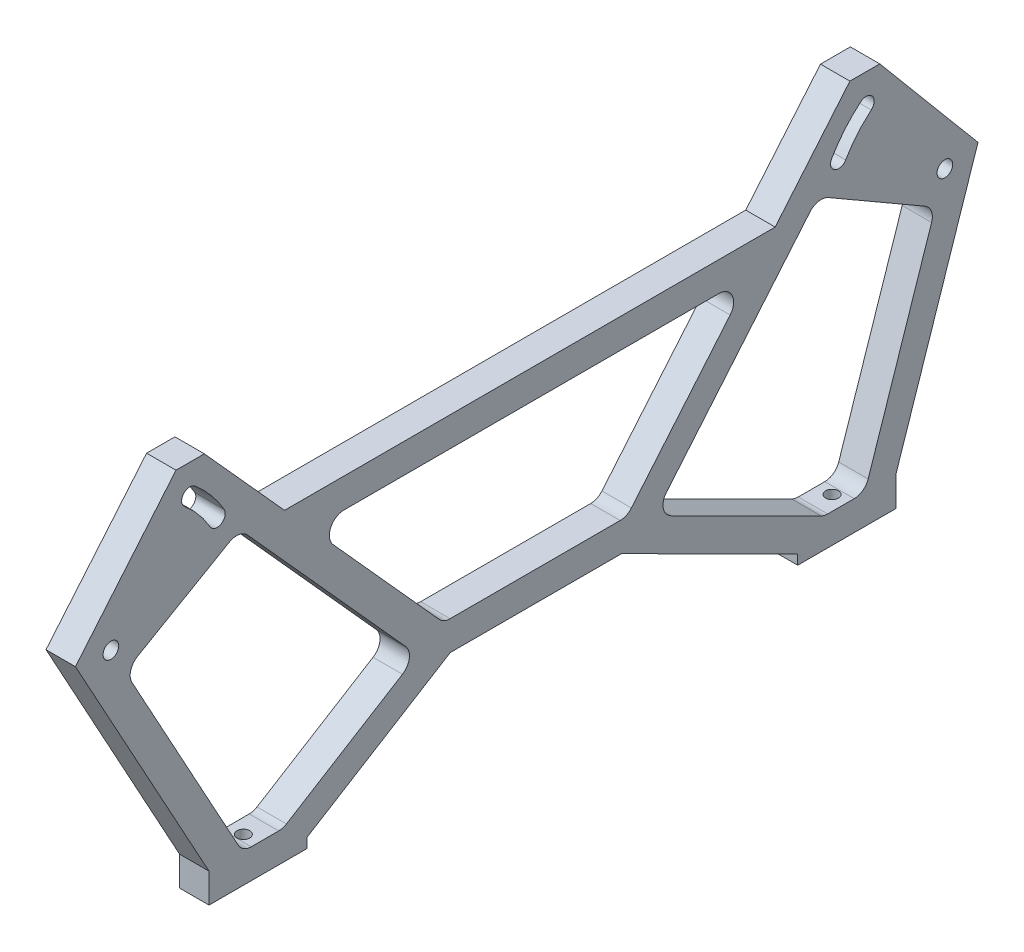
SolidWorks part; units mm, degrees
ref_plane "Front Plane" through (0, 0, 0) normal (0, 0, 1) x (1, 0, 0)
ref_plane "Top Plane" through (0, 0, 0) normal (0, 1, 0) x (1, 0, 0)
ref_plane "Right Plane" through (0, 0, 0) normal (1, 0, 0) x (0, 0, -1)
sketch "Sketch1" plane through (0, 0, 0) normal (1, 0, 0) x (0, 0, -1)
  line L0 (-65, 0) -> (-45, 0)
  line L1 (-45, 0) -> (-45, 2)
  line L2 (-65, 0) -> (-65, 6)
  line L3 (55, 0) -> (75, 0)
  line L4 (75, 0) -> (75, 6)
  line L5 (55, 0) -> (55, 2)
  line L6 (-85, 55) -> (-65.8489, 71.0697) construction
  line L7 (65.8489, 71.0697) -> (85, 55) construction
  line L8 (-68.9303, 74.1511) -> (-85, 55) construction
  line L9 (-85, 55) -> (-63.3494, 67.5) construction
  line L10 (63.3494, 67.5) -> (85, 55) construction
  line L11 (85, 55) -> (68.9303, 74.1511) construction
  line L12 (-65, 6) -> (-92.2327, 55.7147)
  line L13 (-92.2327, 55.7147) -> (-71.7282, 80.1511)
  line L14 (-71.7282, 80.1511) -> (-65.952, 80.1511)
  line L15 (71.7282, 80.1511) -> (91.7528, 56.2866)
  line L16 (91.7528, 56.2866) -> (75, 6)
  line L17 (-58.1588, 6) -> (-49.9434, 6)
  line L18 (-82.1167, 49.7365) -> (-58.7747, 63.213)
  line L19 (-44.2063, 56) -> (45.3715, 56)
  line L20 (59.0991, 63.0257) -> (83.0642, 49.1894)
  line L21 (83.0642, 49.1894) -> (68.6758, 6)
  line L22 (-49.9434, 6) -> (-22.5046, 22.931)
  line L23 (25.8015, 23.343) -> (59.0991, 63.0257)
  line L24 (-15.8286, 20) -> (19.0801, 20)
  line L25 (45.3715, 56) -> (20.1985, 26)
  line L26 (20.1985, 26) -> (-17.1942, 26)
  line L27 (-17.1942, 26) -> (-44.2063, 56)
  line L28 (19.0801, 20) -> (55, 2)
  line L29 (-58.7747, 63.213) -> (-22.5046, 22.931)
  line L30 (-15.8286, 20) -> (-45, 2)
  line L31 (-58.1588, 6) -> (-82.1167, 49.7365)
  line L32 (68.6758, 6) -> (60.4103, 6)
  line L33 (60.4103, 6) -> (25.8015, 23.343)
  line L34 (-15.8286, 20) -> (-26.5479, 31.9049) construction
  line L35 (19.0801, 20) -> (32.4361, 35.917) construction
  line L36 (-65.952, 80.1511) -> (-49.6087, 62)
  line L37 (-49.6087, 62) -> (50.4061, 62)
  line L38 (50.4061, 62) -> (65.6367, 80.1511)
  line L39 (65.6367, 80.1511) -> (71.7282, 80.1511)
  circle A0 centre (-85, 55) radius 1.6
  circle A1 centre (85, 55) radius 1.6
  arc A2 (-68.9303, 74.1511) -> (-63.3494, 67.5) centre (-85, 55) cw construction
  arc A3 (-61.9204, 68.325) -> (-67.8697, 75.4151) centre (-85, 55) ccw
  arc A4 (-64.7783, 66.675) -> (-69.9909, 72.8871) centre (-85, 55) ccw
  arc A5 (-64.7783, 66.675) -> (-61.9204, 68.325) centre (-63.3494, 67.5) ccw
  arc A6 (-67.8697, 75.4151) -> (-69.9909, 72.8871) centre (-68.9303, 74.1511) ccw
  arc A7 (63.3494, 67.5) -> (68.9303, 74.1511) centre (85, 55) cw construction
  arc A8 (67.8697, 75.4151) -> (61.9204, 68.325) centre (85, 55) ccw
  arc A9 (69.9909, 72.8871) -> (64.7783, 66.675) centre (85, 55) ccw
  arc A10 (69.9909, 72.8871) -> (67.8697, 75.4151) centre (68.9303, 74.1511) ccw
  arc A11 (61.9204, 68.325) -> (64.7783, 66.675) centre (63.3494, 67.5) ccw
  point P18 (-65.8489, 71.0697)
  point P28 (65.8489, 71.0697)
  dimension "D11" = 3.2
  dimension "D12" = 1.65
  dimension "D1" = 6
  dimension "D2" = 20
  dimension "D3" = 45
  dimension "D4" = 100
  dimension "D5" = 25
  dimension "D6" = 40
  dimension "D7" = 40
  dimension "D8" = 85
  dimension "D9" = 85
  dimension "D10" = 55
  dimension "D13" = 10
  dimension "D14" = 10
  dimension "D15" = 6
  dimension "D16" = 6
  dimension "D17" = 6
  dimension "D18" = 6
  dimension "D19" = 6
  dimension "D20" = 6
  dimension "D21" = 6
  dimension "D22" = 6
  dimension "D23" = 6
  dimension "D24" = 6
  dimension "D25" = 6
  dimension "D26" = 6
  dimension "D27" = 6
  dimension "D28" = 6
  dimension "D29" = 6
  dimension "D30" = 6
  dimension "D31" = 3
  dimension "D32" = 3
  dimension "D33" = 20
  dimension "D34" = 2
  dimension "D35" = 6
  dimension "D36" = 30
  dimension "D37" = 6
  dimension "D38" = 6
  dimension "D39" = 132
extrude "Boss-Extrude1" add sketch "Sketch1" along normal blind 6
fillet "Fillet1" radius 3 14 edges at (3, 49.1894, -83.0642) (3, 63.0257, -59.0991) (3, 26, 17.1942) (3, 26, -20.1985) (3, 56, -45.3715) (3, 56, 44.2063) (3, 49.7365, 82.1167) (3, 63.213, 58.7747) (3, 23.343, -25.8015) (3, 6, -68.6758) (3, 6, -60.4103) (3, 6, 49.9434) (3, 6, 58.1588) (3, 22.931, 22.5046)
sketch "Sketch2" plane through (0, 0, 0) normal (0, -1, 0) x (1, 0, 0)
  line L0 (6, -55) -> (6, -75) construction
  line L1 (6, -75) -> (0, -75) construction
  line L2 (6, 65) -> (0, 65) construction
  circle A0 centre (3, 55) radius 1.3
  circle A1 centre (3, -65) radius 1.3
  dimension "D1" = 2.6
  dimension "D2" = 3
  dimension "D3" = 10
  dimension "D4" = 10
extrude "Cut-Extrude1" cut sketch "Sketch2" against normal up to next
